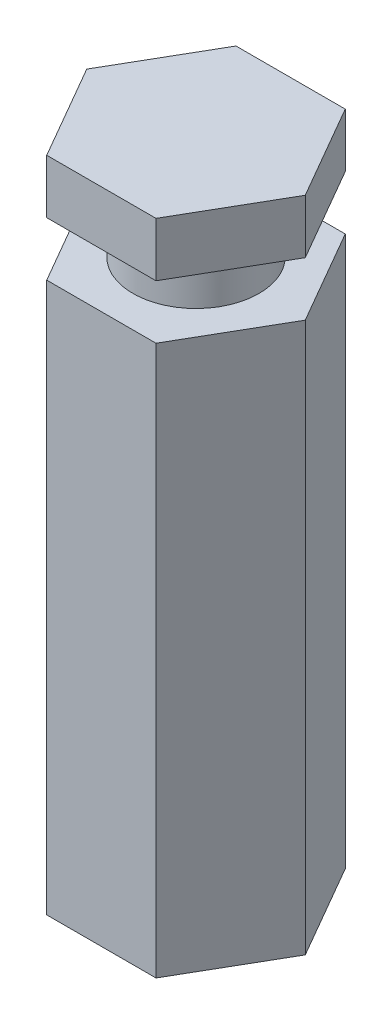
SolidWorks part; units mm, degrees
ref_plane "Front Plane" through (0, 0, 0) normal (0, 0, 1) x (1, 0, 0)
ref_plane "Top Plane" through (0, 0, 0) normal (0, 1, 0) x (1, 0, 0)
ref_plane "Right Plane" through (0, 0, 0) normal (1, 0, 0) x (0, 0, -1)
sketch "Sketch1" plane through (0, 0, 0) normal (0, 1, 0) x (1, 0, 0)
  line L1 (12.1244, 0) -> (6.0622, 10.5)
  line L2 (6.0622, 10.5) -> (-6.0622, 10.5)
  line L3 (-6.0622, 10.5) -> (-12.1244, 0)
  line L4 (-12.1244, 0) -> (-6.0622, -10.5)
  line L5 (-6.0622, -10.5) -> (6.0622, -10.5)
  line L6 (6.0622, -10.5) -> (12.1244, 0)
  circle A0 centre (0, 0) radius 10.5 construction
  circle A1 centre (0, 0) radius 7
  dimension "D1" = 21
  dimension "D2" = 14
extrude "Boss-Extrude3" add sketch "Sketch1" along normal blind 73 contours L5 L6 L1 L2 L3 L4 A1 | A1 region at (8.8155, 0, 5.0896) region at (0, 0, 0)
sketch "Sketch20" plane through (9.0933, 0, -5.25) normal (0.866, 0, -0.5) x (-0.5, 0, -0.866)
  line L1 (-30.41, 67) -> (29.0747, 67)
  line L2 (-30.41, 67) -> (-30.41, 61)
  line L3 (-30.41, 61) -> (29.0747, 61)
  line L4 (29.0747, 67) -> (29.0747, 61)
  line L5 (-6.0622, 0) -> (6.0622, 0) construction
  dimension "D1" = 6
  dimension "D2" = 61
extrude "Cut-Extrude2" cut sketch "Sketch20" against normal blind 73
extrude "Boss-Extrude4" add sketch "Sketch1<5>" along normal blind 67 contours A1 region at (0, 0, 0)
sketch "Sketch1<5>" plane through (0, 0, 0) normal (0, 1, 0) x (1, 0, 0) same geometry as "Sketch1"
